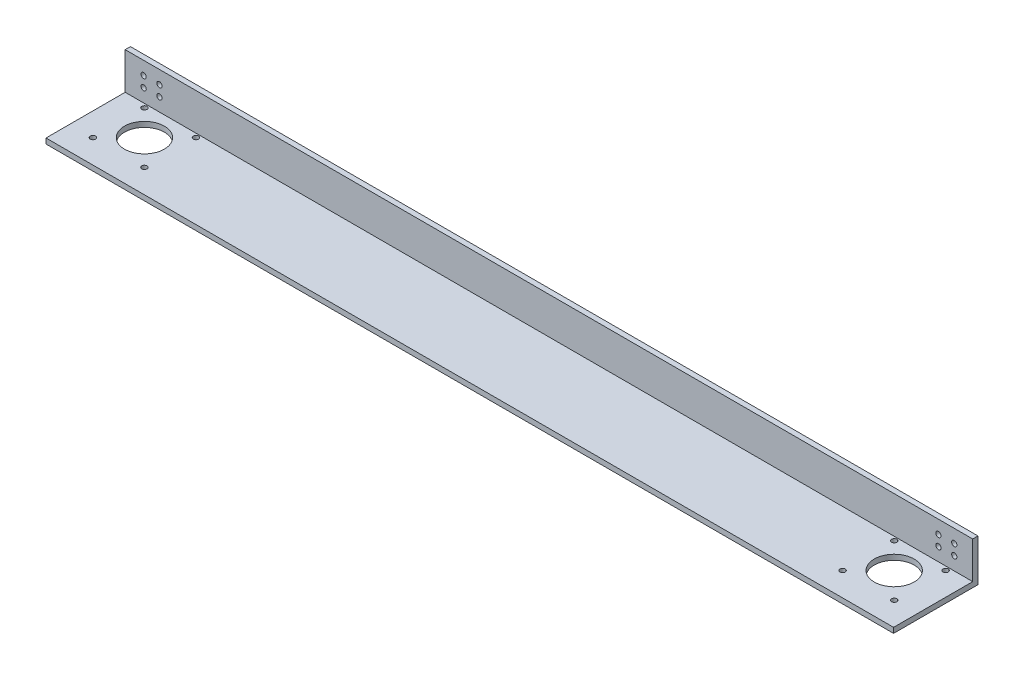
SolidWorks part; units mm, degrees
ref_plane "Front Plane" through (0, 0, 0) normal (0, 0, 1) x (1, 0, 0)
ref_plane "Top Plane" through (0, 0, 0) normal (0, 1, 0) x (1, 0, 0)
ref_plane "Right Plane" through (0, 0, 0) normal (1, 0, 0) x (0, 0, -1)
sketch "Sketch1" plane through (0, 0, 0) normal (1, 0, 0) x (0, 0, -1)
  line L0 (0, 0) -> (-50.8, 0)
  line L1 (-50.8, 0) -> (-50.8, 3.175)
  line L2 (-50.8, 3.175) -> (-3.175, 3.175)
  line L3 (-3.175, 3.175) -> (-3.175, 25.4)
  line L4 (-3.175, 25.4) -> (0, 25.4)
  line L5 (0, 25.4) -> (0, 0)
  dimension "LHeight" = 25.4
  dimension "LWidth" = 50.8
  dimension "LMaterialThickness" = 3.175
  dimension "D1" = 47.625
  dimension "D2" = 22.225
  dimension "D3" = 3.175
extrude "Boss-Extrude1" add sketch "Sketch1" along normal blind 510
sketch "BotthomHoles-Sketch2" plane through (0, 3.175, 0) normal (0, 1, 0) x (1, 0, 0)
  line L2 (0, -3.175) -> (0, -50.8) construction
  line L3 (510, -3.175) -> (510, -50.8) construction
  circle A0 centre (29.425, -21) radius 12
  circle A1 centre (480.575, -21) radius 12
  circle A2 centre (13.925, -5.5) radius 1.5875
  circle A3 centre (44.925, -5.5) radius 1.5875
  circle A4 centre (465.075, -5.5) radius 1.5875
  circle A5 centre (496.075, -5.5) radius 1.5875
  circle A6 centre (13.925, -36.5) radius 1.5875
  circle A7 centre (44.925, -36.5) radius 1.5875
  circle A8 centre (465.075, -36.5) radius 1.5875
  circle A9 centre (496.075, -36.5) radius 1.5875
  dimension "D9" = 3.175
  dimension "D10" = 24
  dimension "D2" = 5.5
  dimension "D3" = 31
  dimension "D4" = 15.5
  dimension "D5" = 15.5
  dimension "D6" = 31
  dimension "D7" = 15.5
  dimension "D13" = 29.425
  dimension "D8" = 31
  dimension "D11" = 29.425
extrude "BottomHoles-Cut-Extrude1" cut sketch "BotthomHoles-Sketch2" against normal through all
sketch "SideHoles-Sketch3" plane through (0, 0, 0) normal (0, 0, -1) x (-1, 0, 0)
  line L1 (-510, 25.4) -> (0, 25.4) construction
  line L2 (0, 0) -> (0, 25.4) construction
  line L3 (-510, 0) -> (-510, 25.4) construction
  circle A0 centre (-498.8875, 17.4625) radius 1.5875
  circle A1 centre (-489.3625, 17.4625) radius 1.5875
  circle A2 centre (-498.8875, 11.1125) radius 1.5875
  circle A3 centre (-489.3625, 11.1125) radius 1.5875
  circle A4 centre (-11.1125, 11.1125) radius 1.5875
  circle A5 centre (-20.6375, 11.1125) radius 1.5875
  circle A6 centre (-20.6375, 17.4625) radius 1.5875
  circle A7 centre (-11.1125, 17.4625) radius 1.5875
  dimension "D7" = 3.175
  dimension "D4" = 11.1125
  dimension "D3" = 7.9375
  dimension "D1" = 11.1125
  dimension "D2" = 20.6375
  dimension "D6" = 20.6375
  dimension "D5" = 11.1125
extrude "SideHoles-Cut-Extrude2" cut sketch "SideHoles-Sketch3" against normal through all
equation "\"MidBackRailWidth\"= 2.00in"
equation "\"MidBackRailHeight\"= 1.00in"
equation "\"RailThickness\"= .125in'Spec"
equation "\"SideRailHoleY1FromEdge\"= \"HoleOffsetFromEdge\""
equation "\"SideRailHoleX1FromSide\"= \"HoleOffsetFromSide\""
equation "\"StepperHoleDiameter\"= 24mm"
equation "\"StepperMountingHoleDiameter\"= 3.175mm"
equation "\"StepperMountingHoleDistance\"= 31mm'Spec"
equation "\"VSWidth\"= 1.25in'Spec"
equation "\"StepperMountingHoleOffsetFromLeftRightEdge\"= \"StepperMountingHoleOffsetFromItsSide\""
equation "\"HoleOffsetFromEdge\"= \"RailThickness\" * 2.5"
equation "\"HoleOffsetFromSide\"= \"RailThickness\" * 3.5"
equation "\"StepperMountingHoleOffsetFromItsSide\"= 5.5mm'Spec"
equation "\"SideRailHoleX2FromSide\"= \"VSWidth\" - \"HoleOffsetFromEdge\" - \"RailThickness\"'Equals 20.6375"
equation "\"FasteningHoleDiameter\"= .125in"
equation "\"SideRailHoleY2FromSide\"= \"HoleOffsetFromSide\""
equation "\"FrontBackRailLength\"= 510mm"
equation "\"LHeight@Sketch1\"=\"MidBackRailHeight\""
equation "\"LWidth@Sketch1\"=\"MidBackRailWidth\""
equation "\"D2@BotthomHoles-Sketch2\" = \"StepperMountingHoleOffsetFromLeftRightEdge\""
equation "\"D3@BotthomHoles-Sketch2\" = \"StepperMountingHoleDistance\""
equation "\"D4@BotthomHoles-Sketch2\" = \"StepperMountingHoleDistance\" / 2"
equation "\"D5@BotthomHoles-Sketch2\" = \"StepperMountingHoleDistance\" / 2"
equation "\"D6@BotthomHoles-Sketch2\" = \"StepperMountingHoleDistance\""
equation "\"D7@BotthomHoles-Sketch2\" = \"StepperMountingHoleDistance\" / 2"
equation "\"D9@BotthomHoles-Sketch2\" = \"StepperMountingHoleDiameter\""
equation "\"D10@BotthomHoles-Sketch2\" = \"StepperHoleDiameter\""
equation "\"D4@SideHoles-Sketch3\" = \"SideRailHoleY2FromSide\""
equation "\"D7@SideHoles-Sketch3\" = \"FasteningHoleDiameter\""
equation "\"D1@Boss-Extrude1\"= \"FrontBackRailLength\""
equation "\"D3@SideHoles-Sketch3\"=\"SideRailHoleY1FromEdge\""
equation "\"D1@SideHoles-Sketch3\"=\"SideRailHoleX1FromSide\""
equation "\"D2@SideHoles-Sketch3\"= \"SideRailHoleX2FromSide\""
equation "\"D6@SideHoles-Sketch3\"=\"SideRailHoleX2FromSide\""
equation "\"D5@SideHoles-Sketch3\"=\"SideRailHoleX1FromSide\""
equation "\"StepperHoleToAlignHorizontallyWithGantryBlock\"= \"MidRailToAlignWithGantryBlock\" + \"RailThickness\"'MidSideRail buts up against MidBackRail"
equation "\"D13@BotthomHoles-Sketch2\"=\"StepperHoleToAlignHorizontallyWithGantryBlock\" "
equation "\"D8@BotthomHoles-Sketch2\"=\"StepperMountingHoleDistance\""
equation "\"D11@BotthomHoles-Sketch2\"=\"StepperHoleToAlignHorizontallyWithGantryBlock\" "
equation "\"LinearGBWithRailDepth\"= 12.75mm'Spec"
equation "\"GABDistanceFromBackToFirstPulley\"= 13.5mm"
equation "\"MidRailToAlignWithGantryBlock\"= \"LinearGBWithRailDepth\" + \"GABDistanceFromBackToFirstPulley\"'All outside cogs must align"
